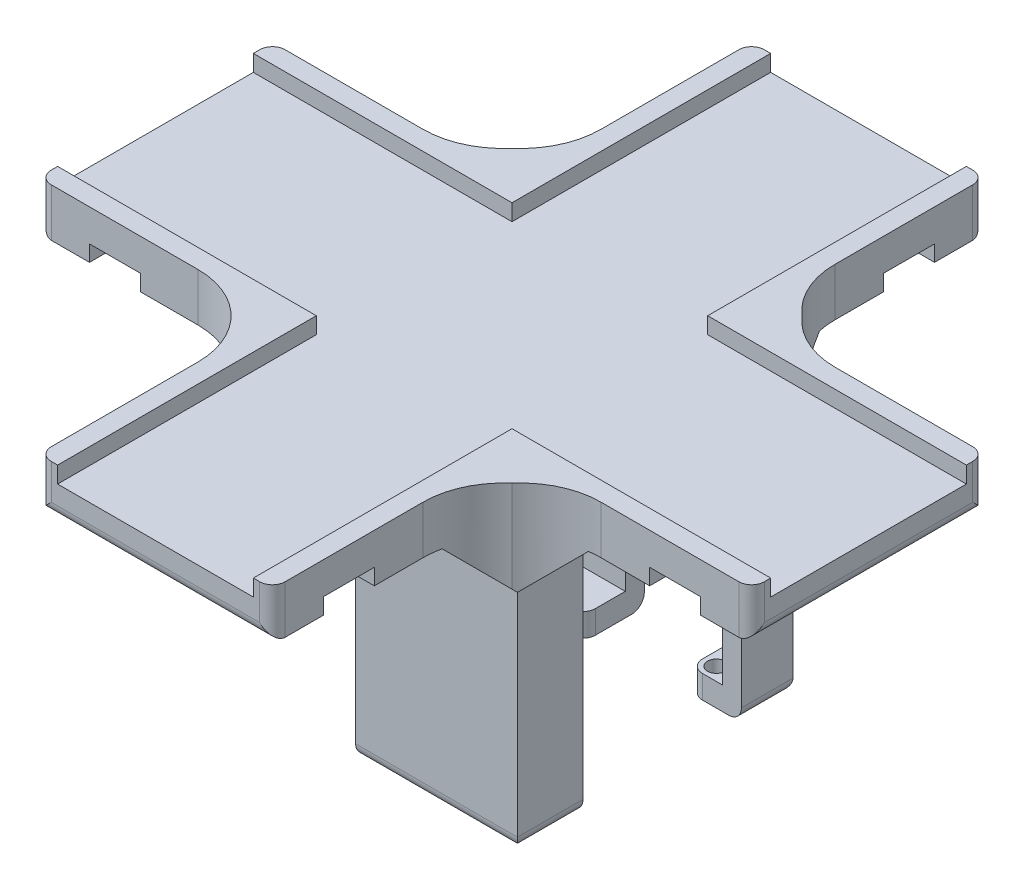
SolidWorks part; units mm, degrees
ref_plane "Front Plane" through (0, 0, 0) normal (0, 0, 1) x (1, 0, 0)
ref_plane "Top Plane" through (0, 0, 0) normal (0, 1, 0) x (1, 0, 0)
ref_plane "Right Plane" through (0, 0, 0) normal (1, 0, 0) x (0, 0, -1)
sketch "Sketch1" plane through (0, 0, 0) normal (0, 1, 0) x (1, 0, 0)
  line L1 (-14.5813, 44.45) -> (14.5813, 44.45)
  line L2 (-14.5813, 44.45) -> (-14.5813, -44.45)
  line L3 (-14.5813, -44.45) -> (14.5813, -44.45)
  line L4 (14.5813, 44.45) -> (14.5813, -44.45)
  line L5 (0, -44.45) -> (0, 44.45) construction
  line L6 (-14.5812, 0) -> (14.5812, 0) construction
  line L7 (-44.45, -14.5813) -> (44.45, -14.5813)
  line L8 (-44.45, -14.5813) -> (-44.45, 14.5812)
  line L9 (-44.45, 14.5812) -> (44.45, 14.5813)
  line L10 (44.45, -14.5813) -> (44.45, 14.5813)
  line L11 (0, 14.5813) -> (0, -14.5813) construction
  line L12 (-44.45, 0) -> (44.45, 0) construction
  point P0 (0, 0)
  point P4 (0, 0)
  dimension "D1" = 29.1625
  dimension "D2" = 88.9
extrude "Boss-Extrude1" add sketch "Sketch1" along normal mid plane 6 contours L7 L2 L3 L4 | L9 L8 L7 L2 | L9 L2 L7 L4 | L2 L9 L4 L1 | L7 L10 L9 L4 region at (0, 0, -29.5156) region at (0, 0, 0) region at (-29.5156, 0, 0) region at (29.5156, 0, 0) region at (0, 0, 29.5156)
sketch "Sketch2" plane through (0, 3, 0) normal (0, 1, 0) x (1, 0, 0)
  line L0 (-14.5813, 44.45) -> (14.5813, 44.45) construction
  line L1 (-44.45, -14.5813) -> (-44.45, 14.5812) construction
  line L2 (-14.5813, -44.45) -> (14.5813, -44.45) construction
  line L3 (44.45, -14.5813) -> (44.45, 14.5813) construction
  line L48 (12.2, -44.45) -> (12.2, -12.2)
  line L49 (12.2, -12.2) -> (44.45, -12.2)
  line L50 (44.45, -12.2) -> (44.45, 12.2)
  line L51 (44.45, 12.2) -> (12.2, 12.2)
  line L52 (12.2, 12.2) -> (12.2, 44.45)
  line L53 (12.2, 44.45) -> (-12.2, 44.45)
  line L54 (-12.2, 44.45) -> (-12.2, 12.2)
  line L55 (-12.2, 12.2) -> (-44.45, 12.2)
  line L56 (-44.45, 12.2) -> (-44.45, -12.2)
  line L57 (-44.45, -12.2) -> (-12.2, -12.2)
  line L58 (-12.2, -12.2) -> (-12.2, -44.45)
  line L59 (-12.2, -44.45) -> (12.2, -44.45)
  dimension "D1" = 24.4
extrude "Cut-Extrude1" cut sketch "Sketch2" against normal blind 2.05
sketch "Sketch3" plane through (0, -34.5, 0) normal (0, -1, 0) x (1, 0, 0)
  line L0 (-17.855, -17.175) -> (-0.68, -17.175)
  line L5 (14.68, 14) -> (-2.32, 14) construction
  line L6 (14.68, 14) -> (14.68, 9) construction
  line L7 (14.68, 9) -> (-2.32, 9)
  line L8 (-2.32, 14) -> (-2.32, 9)
  line L9 (14.68, 14) -> (-2.32, 9) construction
  line L10 (14.68, 9) -> (-2.32, 14) construction
  line L11 (-14.68, -14) -> (-0.68, -14) construction
  line L12 (-14.68, -14) -> (-14.68, -9.5) construction
  line L13 (-14.68, -9.5) -> (-0.68, -9.5)
  line L14 (-0.68, -14) -> (-0.68, -9.5)
  line L15 (-14.68, -14) -> (-0.68, -9.5) construction
  line L16 (-14.68, -9.5) -> (-0.68, -14) construction
  line L17 (14.68, -14) -> (11.43, -14) construction
  line L18 (14.68, -14) -> (14.68, -10.75) construction
  line L19 (14.68, -10.75) -> (11.43, -10.75)
  line L20 (11.43, -14) -> (11.43, -10.75)
  line L21 (14.68, -14) -> (11.43, -10.75) construction
  line L22 (14.68, -10.75) -> (11.43, -14) construction
  line L23 (-17.855, -17.175) -> (-17.855, -9.5)
  line L24 (17.855, -17.175) -> (17.855, -10.75)
  line L25 (17.855, -17.175) -> (11.43, -17.175)
  line L26 (17.855, 17.175) -> (-2.32, 17.175)
  line L27 (17.855, 17.175) -> (17.855, 9)
  line L28 (-17.855, -9.5) -> (-14.68, -9.5)
  line L29 (-0.68, -14) -> (-0.68, -17.175)
  line L30 (-2.32, 14) -> (-2.32, 17.175)
  line L31 (14.68, 9) -> (17.855, 9)
  line L32 (14.68, -10.75) -> (17.855, -10.75)
  line L33 (11.43, -14) -> (11.43, -17.4186)
  circle A0 centre (13.08, -12.4) radius 1.1 construction
  circle A1 centre (13.08, 12.4) radius 1.1 construction
  circle A2 centre (13.08, -12.4) radius 1.1
  circle A3 centre (13.08, 12.4) radius 1.1
  point P10 (6.18, 11.5)
  point P15 (-7.68, -11.75)
  point P20 (13.055, -12.375)
  line M8 (14.68, -14) -> (14.68, 14)
  line M9 (14.68, 14) -> (-14.68, 14)
  line M10 (-14.68, 14) -> (-14.68, -14)
  line M11 (-14.68, -14) -> (14.68, -14)
  circle M12 centre (13.08, -12.4) radius 1.1
  circle M13 centre (13.08, 12.4) radius 1.1
  dimension "D1" = 5
  dimension "D2" = 17
  dimension "D3" = 14
  dimension "D4" = 4.5
  dimension "D5" = 3.25
  dimension "D6" = 3.25
  dimension "D7" = 3.175
extrude "Boss-Extrude2" add sketch "Sketch3" along normal blind 2.88 separate body contours L29 L28 L23 L0 M11 M10 | L14 L13 M11 M10 | L33 L25 L24 L32 M11 M8 | L20 L19 M11 M8 M12 | L8 L7 M9 M8 M13 | L31 L27 L26 L30 M8 M9 region at (-10.7208, -34.5, -14.7908) region at (-7.68, -34.5, -11.75) region at (15.1884, -34.5, -14.5084) region at (11.476, -34.5, -12.375) region at (5.857, -34.5, 11.4579) region at (9.4557, -34.5, 14.7757)
sketch "Sketch4" plane through (0, -34.5, 0) normal (0, 1, 0) x (1, 0, 0)
  line L6 (-17.855, 17.175) -> (-0.68, 17.175) construction
  line L7 (17.855, 17.175) -> (11.43, 17.175) construction
  line L8 (17.855, 17.175) -> (17.855, 10.75) construction
  line L9 (15.48, 14.8) -> (-14.68, 14.8)
  line L10 (-14.68, -14.8) -> (15.48, -14.8)
  line L11 (15.48, -14.8) -> (15.48, 14.8)
  line L12 (15.48, 14.8) -> (11.43, 14.8)
  line L13 (-2.32, -14.8) -> (15.48, -14.8)
  line L14 (15.48, -14.8) -> (15.48, -9)
  line L15 (17.855, -17.175) -> (17.855, -9) construction
  line L16 (17.855, -17.175) -> (-2.32, -17.175) construction
  line L17 (-17.855, 17.175) -> (-0.68, 17.175)
  line L18 (17.855, 17.175) -> (11.43, 17.175)
  line L19 (17.855, 17.175) -> (17.855, 10.75)
  line L20 (17.855, -17.175) -> (17.855, -9)
  line L21 (17.855, -17.175) -> (-2.32, -17.175)
  line L22 (-2.32, -17.175) -> (-2.32, -14.8)
  line L23 (-2.32, -17.175) -> (-2.32, -9) construction
  line L24 (17.855, -9) -> (15.48, -9)
  line L25 (17.855, -9) -> (-2.32, -9) construction
  line L26 (17.855, 10.75) -> (15.48, 10.75)
  line L27 (11.43, 10.75) -> (17.855, 10.75) construction
  line L28 (11.43, 17.175) -> (11.43, 14.8)
  line L29 (-0.68, 17.175) -> (-0.68, 14.8)
  line L30 (-0.68, 9.5) -> (-0.68, 17.175) construction
  line L31 (-17.855, 17.175) -> (-17.855, 14.8)
  line L32 (-17.855, 17.175) -> (-17.855, 9.5) construction
  line L33 (15.48, 10.75) -> (15.48, 14.8)
  line L34 (-0.68, 14.8) -> (-17.855, 14.8)
  line M4 (-2.32, -17.175) -> (17.855, -17.175)
  line M5 (17.855, -17.175) -> (17.855, -9)
  line M6 (17.855, -9) -> (-2.32, -9)
  line M7 (-2.32, -9) -> (-2.32, -17.175)
  dimension "D1" = 0.8
sketch "Sketch6" plane through (0, -3, 0) normal (0, -1, 0) x (-1, 0, 0)
  line L7 (-14.5813, -14.5813) -> (-18.0813, -14.5813)
  line L8 (-14.5813, -14.5813) -> (-14.5813, -18.0813)
  line L9 (-14.5813, -18.0813) -> (-18.0813, -18.0813)
  line L10 (-18.0813, -14.5813) -> (-18.0813, -18.0813)
  line L11 (-14.5813, -14.5813) -> (-18.0813, -18.0813) construction
  line L12 (-14.5813, -18.0813) -> (-18.0813, -14.5813) construction
  line L13 (-14.5813, 14.5812) -> (-18.0813, 14.5812)
  line L14 (-14.5813, 14.5812) -> (-14.5813, 18.0813)
  line L15 (-14.5813, 18.0813) -> (-18.0813, 18.0813)
  line L16 (-18.0813, 14.5812) -> (-18.0813, 18.0813)
  line L17 (-14.5813, 14.5812) -> (-18.0813, 18.0813) construction
  line L18 (-14.5813, 18.0813) -> (-18.0813, 14.5812) construction
  line L19 (14.5813, 14.5812) -> (18.0813, 14.5813)
  line L20 (14.5813, 14.5812) -> (14.5813, 18.0813)
  line L21 (14.5813, 18.0813) -> (18.0813, 18.0813)
  line L22 (18.0813, 14.5813) -> (18.0813, 18.0813)
  line L23 (14.5813, 14.5812) -> (18.0813, 18.0813) construction
  line L24 (14.5813, 18.0813) -> (18.0813, 14.5813) construction
  point P10 (-16.3313, -16.3313)
  point P16 (-16.3313, 16.3313)
  point P22 (16.3313, 16.3313)
  dimension "D1" = 3.5
extrude "Boss-Extrude3" add sketch "Sketch6" against normal up to surface (6 mm away) up to face at (-23.7437, 3, 23.7438)
extrude "Boss-Extrude4" add sketch "Sketch4" along normal up to surface (31.5 mm away) contours L33 L26 L19 L18 L28 L12 | L14 L13 M7 M4 M5 M6 | L34 L29 L17 L31 region at (-9.2675, -34.5, -15.9875) region at (9.7548, -34.5, 15.0748) region at (13.455, -34.5, -14.8909) up to face at (2.009, -3, -2.009)
fillet "Fillet1" radius 10 7 edges at (-14.5813, 0, 14.5813) (-14.5813, 0, -18.0813) (-18.0813, 0, -14.5812) (14.5813, 0, -18.0813) (18.0813, 0, -14.5812) (18.0813, 0, 14.5813) (14.5813, 0, 18.0813)
chamfer "Chamfer1" distance 6.35 angle 45 6 edges at (7.7675, -3, 17.175) (17.855, -3, 13.0875) (17.855, -3, -13.9625) (14.6425, -3, -17.175) (-17.855, -3, -15.9875) (-9.2675, -3, -17.175)
fillet "Fillet2" radius 1.5875 4 edges at (-17.855, -35.94, -9.5) (-0.68, -35.94, -9.5) (-2.32, -35.94, 9) (11.43, -35.94, -10.75)
fillet "Fillet3" radius 1.5875 5 edges at (17.855, -37.38, -13.9625) (17.855, -37.38, 13.0875) (14.6425, -37.38, -17.175) (-9.2675, -37.38, -17.175) (7.7675, -37.38, 17.175)
sketch "Sketch7" plane through (0, -3, 0) normal (0, -1, 0) x (-1, 0, 0)
  line L0 (14.5813, -24.5813) -> (14.5813, -44.45) construction
  line L1 (14.5813, -38.1) -> (-14.5813, -38.1)
  line L2 (14.5813, -38.1) -> (14.5813, -31.75)
  line L3 (14.5813, -31.75) -> (-14.5813, -31.75)
  line L4 (-14.5813, -38.1) -> (-14.5813, -31.75)
  line L5 (14.5813, -38.1) -> (-14.5813, -31.75) construction
  line L6 (14.5813, -31.75) -> (-14.5813, -38.1) construction
  line L7 (-14.5813, -25.6806) -> (-14.5813, -44.45) construction
  line L8 (-25.6806, -14.5813) -> (-44.45, -14.5813) construction
  line L9 (-31.75, -14.5813) -> (-38.1, -14.5813)
  line L10 (-31.75, -14.5813) -> (-31.75, 14.5812)
  line L11 (-31.75, 14.5812) -> (-38.1, 14.5812)
  line L12 (-38.1, -14.5813) -> (-38.1, 14.5812)
  line L13 (-31.75, -14.5813) -> (-38.1, 14.5812) construction
  line L14 (-31.75, 14.5812) -> (-38.1, -14.5813) construction
  line L15 (-25.6806, 14.5812) -> (-44.45, 14.5813) construction
  line L16 (14.5813, 44.45) -> (14.5813, 25.6806) construction
  line L17 (14.5813, 31.75) -> (-14.5813, 31.75)
  line L18 (14.5813, 31.75) -> (14.5813, 38.1)
  line L19 (14.5813, 38.1) -> (-14.5813, 38.1)
  line L20 (-14.5813, 31.75) -> (-14.5813, 38.1)
  line L21 (14.5813, 31.75) -> (-14.5813, 38.1) construction
  line L22 (14.5813, 38.1) -> (-14.5813, 31.75) construction
  line L23 (-14.5813, 44.45) -> (-14.5813, 25.6806) construction
  line L24 (44.45, -14.5813) -> (24.5812, -14.5813) construction
  line L25 (38.1, 14.5812) -> (31.75, 14.5812)
  line L26 (38.1, 14.5812) -> (38.1, -14.5813)
  line L27 (38.1, -14.5813) -> (31.75, -14.5813)
  line L28 (31.75, 14.5812) -> (31.75, -14.5813)
  line L29 (38.1, 14.5812) -> (31.75, -14.5813) construction
  line L30 (38.1, -14.5813) -> (31.75, 14.5812) construction
  line L31 (44.45, 14.5812) -> (25.6806, 14.5812) construction
  line L32 (44.45, -14.5813) -> (44.45, 14.5812) construction
  line L33 (14.5813, -44.45) -> (-14.5813, -44.45) construction
  line L34 (-44.45, -14.5813) -> (-44.45, 14.5813) construction
  line L35 (14.5813, 44.45) -> (-14.5813, 44.45) construction
  point P4 (0, -34.925)
  point P13 (-34.925, 0)
  point P22 (0, 34.925)
  point P31 (34.925, 0)
  dimension "D1" = 6.35
  dimension "D2" = 6.35
  dimension "D3" = 6.35
  dimension "D4" = 6.35
  dimension "D5" = 6.35
extrude "Cut-Extrude2" cut sketch "Sketch7" against normal blind 2
fillet "Fillet4" radius 1.5875 12 edges at (-14.5813, 0, -44.45) (0, -3, -44.45) (14.5813, 0, -44.45) (44.45, 0, -14.5813) (44.45, -3, 0) (44.45, 0, 14.5813) (14.5813, 0, 44.45) (0, -3, 44.45) (-14.5813, 0, 44.45) (-44.45, 0, -14.5812) (-44.45, -3, 0) (-44.45, 0, 14.5813)
